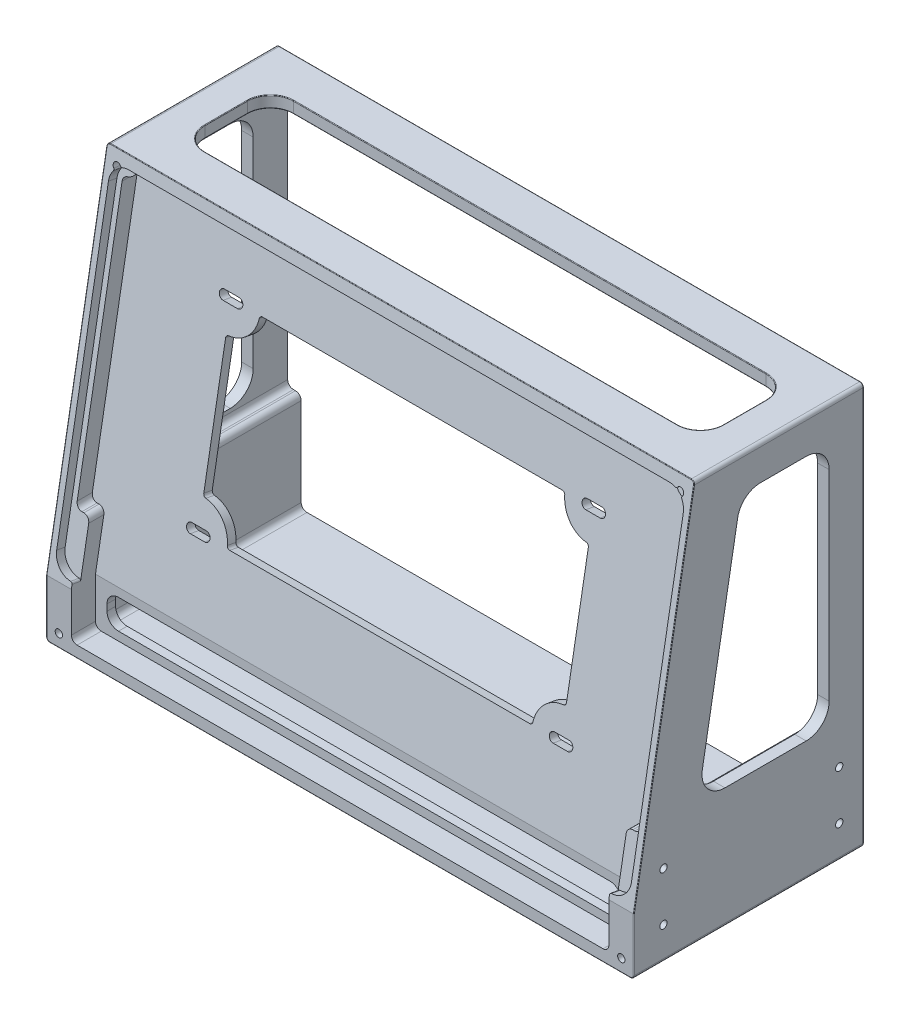
SolidWorks part; units mm, degrees
ref_plane "Спереди" through (0, 0, 0) normal (0, 0, 1) x (1, 0, 0)
ref_plane "Сверху" through (0, 0, 0) normal (0, 1, 0) x (1, 0, 0)
ref_plane "Справа" through (0, 0, 0) normal (1, 0, 0) x (0, 0, -1)
sketch "Эскиз2" plane through (0, 0, 0) normal (0, 0, 1) x (1, 0, 0)
  line L1 (102.25, -69.9) -> (-102.25, -69.9)
  line L2 (102.25, -69.9) -> (102.25, 69.9)
  line L3 (102.25, 69.9) -> (-102.25, 69.9)
  line L4 (-102.25, -69.9) -> (-102.25, 69.9)
  line L5 (102.25, -69.9) -> (-102.25, 69.9) construction
  line L6 (102.25, 69.9) -> (-102.25, -69.9) construction
  point P0 (0, 0)
  dimension "D1" = 204.5
  dimension "D2" = 139.8
extrude "Вытянуть-Тонкостенный1" add sketch "Эскиз2" along normal blind 80 thin
fillet "Скругление1" radius 1.2 8 edges at (98.25, -65.9, 40) (98.25, 65.9, 40) (-98.25, 65.9, 40) (-98.25, -65.9, 40) (-102.25, -69.9, 40) (102.25, -69.9, 40) (102.25, 69.9, 40) (-102.25, 69.9, 40)
sketch "Эскиз11" plane through (0, 0, 80) normal (0, 0, 1) x (1, 0, 0)
  line L0 (101.05, 69.9) -> (-101.05, 69.9) construction
  circle A0 centre (-97.8985, 65.5485) radius 4.3515
  arc A1 (-97.05, 65.9) -> (-98.25, 64.7) centre (-97.05, 64.7) ccw construction
  circle A2 centre (97.8985, 65.5485) radius 4.3515
  arc A3 (98.25, 64.7) -> (97.05, 65.9) centre (97.05, 64.7) ccw construction
  circle A4 centre (97.8985, -65.5485) radius 4.3515
  arc A5 (97.05, -65.9) -> (98.25, -64.7) centre (97.05, -64.7) ccw construction
  circle A6 centre (-97.8985, -65.5485) radius 4.3515
  arc A7 (-98.25, -64.7) -> (-97.05, -65.9) centre (-97.05, -64.7) ccw construction
extrude "Бобышка-Вытянуть6" add sketch "Эскиз11" against normal up to surface (80 mm away) up to face at (0, 0, 0)
sketch "Эскиз3" plane through (-102.25, 0, 0) normal (-1, 0, 0) x (0, 0, 1)
  line L0 (58.8408, 69.9) -> (80, -50.1)
  line L1 (0, 69.9) -> (80, 69.9) construction
  line L2 (80, 68.7) -> (80, -68.7) construction
  line L3 (80, -50.1) -> (80, 69.9)
  line L4 (80, 69.9) -> (58.8408, 69.9)
  dimension "D1" = 10
  dimension "D2" = 120
extrude "Вырез-Вытянуть1" cut sketch "Эскиз3" against normal through all
ref_plane "Плоскость1" through (0, 10.7462, 60.9447) normal (0, 0.1736, 0.9848) x (1, 0, 0)
sketch "Эскиз5" plane through (0, 10.7462, 60.9447) normal (0, 0.1736, 0.9848) x (1, 0, 0)
  line L0 (-52.3265, 30.618) -> (53.95, 30.618)
  line L1 (63.95, 30.618) -> (-62.3265, 30.618) construction
  line L3 (63.95, -35.032) -> (-62.3265, -35.032) construction
  line L4 (-62.3265, 30.618) -> (-62.3265, -35.032) construction
  line L5 (63.95, -35.032) -> (63.95, 30.618) construction
  line L6 (63.95, 20.618) -> (63.95, -25.032)
  line L7 (-62.3265, 20.618) -> (-62.3265, -25.032)
  line L16 (-52.3265, -35.032) -> (53.95, -35.032)
  line L17 (101.05, 58.6205) -> (-101.05, 58.6205) construction
  line L18 (-98.25, -63.2307) -> (-98.25, 49.7977) construction
  line L23 (98.25, -61.3795) -> (-98.25, -61.3795)
  line L24 (98.25, -61.3795) -> (98.25, 58.6205)
  line L25 (98.25, 58.6205) -> (-98.25, 58.6205)
  line L26 (-98.25, -61.3795) -> (-98.25, 58.6205)
  line L27 (98.25, -61.3795) -> (-98.25, 58.6205) construction
  line L28 (98.25, 58.6205) -> (-98.25, -61.3795) construction
  line L29 (98.25, 49.7977) -> (98.25, -63.2307) construction
  arc A0 (-62.3265, 20.618) -> (-52.3265, 30.618) centre (-62.3265, 30.618) ccw
  arc A1 (53.95, 30.618) -> (63.95, 20.618) centre (63.95, 30.618) ccw
  arc A2 (63.95, -25.032) -> (53.95, -35.032) centre (63.95, -35.032) ccw
  arc A3 (-52.3265, -35.032) -> (-62.3265, -25.032) centre (-62.3265, -35.032) ccw
  point P10 (0.8118, -1.3534)
  point P11 (0.8118, -1.3534)
  point P15 (0, -1.3795)
  dimension "D1" = 20
  dimension "D2" = 120
extrude "Бобышка-Вытянуть3" add sketch "Эскиз5" against normal blind 3
hole_wizard "Сверло под метчик  спиральное M31" positions "Трехмерный эскиз1" profile "Эскиз7" hole size "M3x0.5" standard "Ansi Metric"
sketch3d "Трехмерный эскиз1"
  line L0 (63.95, 40.3781, 52.6735) -> (63.95, 40.899, 55.6279) construction
  line L1 (-62.3265, 40.3781, 52.6735) -> (-62.3265, 40.899, 55.6279) construction
  line L2 (-62.3265, -24.2745, 64.0735) -> (-62.3265, -23.7536, 67.0279) construction
  line L3 (63.95, -24.2745, 64.0735) -> (63.95, -23.7536, 67.0279) construction
  point P0 (63.95, 40.3781, 52.6735)
  point P4 (-62.3265, 40.3781, 52.6735)
  point P8 (-62.3265, -24.2745, 64.0735)
  point P12 (63.95, -24.2745, 64.0735)
sketch "Эскиз7" plane through (63.95, 40.3781, 52.6735) normal (1, 0, 0) x (0, 0.9848, -0.1736)
  line L0 (0, 0) -> (0, 9.4464)
  line L1 (0, 9.4464) -> (1.575, 8.5)
  line L2 (1.575, 8.5) -> (1.575, 0)
  line L5 (1.575, 0) -> (0, 0)
  line L10 (0, 9.4464) -> (-1.575, 8.5) construction
  line L11 (0, -6.35) -> (0, 107.95) construction
  dimension "Диаметр отверстия" = 3.15
  dimension "Глубина отверстия" = 8.5
  dimension "Угол заточки сверла" = 118
hole_wizard "Сверло под метчик  спиральное M2.51" positions "Трехмерный эскиз2" profile "Эскиз12" hole size "M2.5x0.45" standard "Ansi Metric"
sketch3d "Трехмерный эскиз2"
  line L0 (97.8985, 65.5485, 14.6109) -> (97.8985, 65.5485, 44.282) construction
  line L1 (-97.8985, -65.5485, 0) -> (-97.8985, -65.5485, 80) construction
  line L2 (97.8985, -65.5485, 0) -> (97.8985, -65.5485, 80) construction
  line L3 (-97.8985, 65.5485, 14.6109) -> (-97.8985, 65.5485, 44.282) construction
  point P0 (97.8985, 65.5485, 0)
  point P8 (-97.8985, -65.5485, 0)
  point P31 (97.8985, -65.5485, 0)
  point P40 (-97.8985, 65.5485, 0)
sketch "Эскиз12" plane through (97.8985, 65.5485, 0) normal (1, 0, 0) x (0, 1, 0)
  line L0 (0, 0) -> (0, 20.7661)
  line L1 (0, 20.7661) -> (1.275, 20)
  line L2 (1.275, 20) -> (1.275, 0)
  line L5 (1.275, 0) -> (0, 0)
  line L10 (0, 20.7661) -> (-1.275, 20) construction
  line L11 (0, -6.35) -> (0, 107.95) construction
  dimension "Диаметр отверстия" = 2.55
  dimension "Глубина отверстия" = 20
  dimension "Угол заточки сверла" = 118
fillet "Скругление2" radius 1 8 edges at (53.95, -24.0141, 65.5507) (63.95, -14.166, 63.8142) (53.95, 40.6386, 54.1507) (63.95, 30.7905, 55.8872) (-52.3265, 40.6386, 54.1507) (-62.3265, 30.7905, 55.8872) (-52.3265, -24.0141, 65.5507) (-62.3265, -14.166, 63.8142)
hole_wizard "Сверло под метчик  спиральное M2.52" positions "Трехмерный эскиз3" profile "Эскиз13" hole size "M2.5x0.45" standard "Ansi Metric"
sketch3d "Трехмерный эскиз3"
  line L0 (-97.8985, -65.5485, 0) -> (-97.8985, -65.5485, 80) construction
  line L1 (97.8985, -65.5485, 0) -> (97.8985, -65.5485, 80) construction
  point P12 (-98.0213, 65.0213, 59.701)
  point P28 (98.0213, 65.0213, 59.701)
  point P36 (-97.8985, -65.5485, 80)
  point P40 (97.8985, -65.5485, 80)
sketch "Эскиз13" plane through (-98.0213, 65.0213, 59.701) normal (1, 0, 0) x (0, -0.9848, 0.1736)
  line L0 (0, 0) -> (0, 9.2661)
  line L1 (0, 9.2661) -> (1.275, 8.5)
  line L2 (1.275, 8.5) -> (1.275, 0)
  line L5 (1.275, 0) -> (0, 0)
  line L10 (0, 9.2661) -> (-1.275, 8.5) construction
  line L11 (0, -6.35) -> (0, 107.95) construction
  dimension "Диаметр отверстия" = 2.55
  dimension "Глубина отверстия" = 8.5
  dimension "Угол заточки сверла" = 118
sketch "Эскиз17" plane through (0, 0, 0) normal (0, 0, -1) x (-1, 0, 0)
  line L0 (-98.25, -31.2113) -> (-93.5471, -31.2113)
  line L1 (-98.25, -61.2113) -> (-98.25, 61.2113) construction
  line L2 (-93.5471, -65.5485) -> (-93.5471, -31.2113)
  line L4 (-98.25, -31.2113) -> (-98.25, -61.2113)
  line L5 (98.25, -61.2113) -> (98.25, -31.2113)
  line L6 (98.25, 61.2113) -> (98.25, -50.2218) construction
  line L7 (98.25, -31.2113) -> (93.5471, -31.2113)
  line L8 (93.5471, -31.2113) -> (93.5471, -65.5485)
  arc A0 (-93.5471, -65.5485) -> (-98.25, -61.2113) centre (-97.8985, -65.5485) ccw
  arc A1 (98.25, -61.2113) -> (93.5471, -65.5485) centre (97.8985, -65.5485) ccw
  dimension "D1" = 30
extrude "Бобышка-Вытянуть7" add sketch "Эскиз17" against normal up to surface (80 mm away) up to face at (-96.6235, -65.5485, 80)
fillet "Скругление3" radius 2 18 edges at (93.5471, -31.2113, 32.6483) (98.25, -31.2113, 32.6483) (-98.25, -31.2113, 32.6483) (-93.5471, -31.2113, 32.6483) (-93.5613, -65.9, 40) (93.5613, -65.9, 40) (-93.5613, 65.9, 24.0866) (-98.25, 61.2113, 24.5) (93.5613, 65.9, 24.0866) (98.25, 61.2113, 24.5) (-93.5471, -31.2113, 74.1715) (-98.25, -31.2113, 72.5062) (93.5471, -31.2113, 74.1715) (98.25, -31.2113, 72.5062) (98.25, 61.2113, 56.2096) (93.5613, 65.9, 55.3828) (-93.5613, 65.9, 55.3828) (-98.25, 61.2113, 56.2096)
hole_wizard "Сверло под метчик  спиральное M30" positions "Трехмерный эскиз5" profile "Эскиз16" hole size "M2.5x0.45" standard "Ansi Metric"
sketch3d "Трехмерный эскиз5"
  circle A0 centre (-104.05, -58.5, 8.4941) radius 1.7 construction
  circle A1 centre (-102.5, -41.5, 8.4941) radius 1.7 construction
  circle A2 centre (-104.05, -58.48, 69.6888) radius 1.7 construction
  circle A3 centre (-104.05, -41.5, 69.6541) radius 1.7 construction
  circle A4 centre (104.05, -58.5, 8.4941) radius 1.7 construction
  circle A5 centre (102.5, -41.5, 8.4941) radius 1.7 construction
  circle A6 centre (104.05, -58.48, 69.6888) radius 1.7 construction
  circle A7 centre (104.05, -41.5, 69.6541) radius 1.7 construction
  point P0 (-102.25, -58.5, 8.4941)
  point P2 (-102.25, -41.5, 8.4941)
  point P4 (-102.25, -41.5, 69.6541)
  point P6 (-102.25, -58.48, 69.6888)
  point P8 (102.25, -41.5, 69.6541)
  point P10 (102.25, -58.48, 69.6888)
  point P12 (102.25, -41.5, 8.4941)
  point P14 (102.25, -58.5, 8.4941)
  point P24 (-105.75, -58.5, 8.4941)
  point P29 (-100.8, -41.5, 8.4941)
  point P33 (-105.75, -58.48, 69.6888)
  point P37 (-105.75, -41.5, 69.6541)
  point P41 (105.75, -58.5, 8.4941)
  point P45 (100.8, -41.5, 8.4941)
  point P49 (105.75, -58.48, 69.6888)
  point P52 (105.75, -41.5, 69.6541)
sketch "Эскиз16" plane through (-102.25, -58.5, 8.4941) normal (0, 1, 0) x (0, 0, 1)
  line L0 (0, 0) -> (0, 7.7661)
  line L1 (0, 7.7661) -> (1.275, 7)
  line L2 (1.275, 7) -> (1.275, 0)
  line L5 (1.275, 0) -> (0, 0)
  line L10 (0, 7.7661) -> (-1.275, 7) construction
  line L11 (0, -6.35) -> (0, 107.95) construction
  dimension "Диаметр отверстия" = 2.55
  dimension "Глубина отверстия" = 7
  dimension "Угол заточки сверла" = 118
sketch "Эскиз18" plane through (-98.25, 0, 0) normal (-1, 0, 0) x (0, 0, 1)
  line L0 (80, -31.2113) -> (76.6694, -31.2113)
  line L1 (59.0524, 68.7) -> (80, -50.1) construction
  line L2 (80, -50.1) -> (76.6694, -31.2113) construction
  line L3 (76.6694, -31.2113) -> (80, -50.1)
  line L4 (80, -50.1) -> (80, -31.2113)
extrude "Вырез-Вытянуть2" cut sketch "Эскиз18" against normal through all
ref_plane "Плоскость2" through (0, 0, 71.6031) normal (0, 0, 1) x (1, 0, 0)
sketch "Эскиз19" plane through (0, 0, 71.6031) normal (0, 0, 1) x (1, 0, 0)
  line L0 (-91.5471, -65.9) -> (91.5471, -65.9) construction
  line L1 (-93.5471, -49.7008) -> (93.5471, -49.7008)
  line L2 (-93.5471, -49.7008) -> (-93.5471, -65.9)
  line L3 (-93.5471, -65.9) -> (93.5471, -65.9)
  line L4 (93.5471, -49.7008) -> (93.5471, -65.9)
extrude "Бобышка-Вытянуть8" add sketch "Эскиз19" against normal blind 3
sketch "Эскиз20" plane through (0, 0, 71.6031) normal (0, 0, 1) x (1, 0, 0)
  line L3 (0, 0) -> (0, -65.9) construction
  line L4 (-91.5471, -65.9) -> (91.5471, -65.9) construction
  line L12 (-93.5471, -49.7008) -> (93.5471, -49.7008) construction
  line L13 (89.5471, -62.9) -> (-89.5471, -62.9)
  line L14 (89.5471, -62.9) -> (89.5471, -52.7008)
  line L15 (89.5471, -52.7008) -> (-89.5471, -52.7008)
  line L16 (-89.5471, -62.9) -> (-89.5471, -52.7008)
  line L17 (89.5471, -62.9) -> (-89.5471, -52.7008) construction
  line L18 (89.5471, -52.7008) -> (-89.5471, -62.9) construction
  line L19 (-91.5471, -65.9) -> (91.5471, -65.9) construction
  line L20 (-93.5471, -50.1) -> (-93.5471, -63.9) construction
  point P0 (0, -57.8004)
  point P14 (-89.5471, -57.8004)
  dimension "D1" = 3
  dimension "D2" = 3
  dimension "D3" = 4
extrude "Вырез-Вытянуть3" cut sketch "Эскиз20" against normal blind 4
hole_wizard "Цековка для винта с внутренним шестигранником M31" positions "Трехмерный эскиз6" profile "Эскиз21" counterbore size "M3" standard "Ansi Metric"
sketch3d "Трехмерный эскиз6"
  circle A0 centre (34.7971, -65.9, 34.3016) radius 1.5 construction
  circle A1 centre (73.8971, -65.9, 34.3016) radius 1.5 construction
  point P16 (34.7971, -69.9, 34.3016)
  point P28 (34.7971, -67.4, 34.3016)
  point P31 (73.8971, -69.9, 34.3016)
  point P38 (73.8971, -67.4, 34.3016)
sketch "Эскиз21" plane through (34.7971, -69.9, 34.3016) normal (1, 0, 0) x (0, 0, -1)
  line L0 (0, 0) -> (0, 9.5215)
  line L1 (0, 9.5215) -> (1.7, 8.5)
  line L2 (1.7, 8.5) -> (1.7, 3)
  line L3 (1.7, 3) -> (3.25, 3)
  line L4 (3.25, 3) -> (3.25, 0)
  line L5 (3.25, 0) -> (0, 0)
  line L10 (0, 9.5215) -> (-1.7, 8.5) construction
  line L11 (0, -6.35) -> (0, 107.95) construction
  dimension "Диаметр отверстия" = 3.4
  dimension "Глубина отверстия" = 8.5
  dimension "Диаметр цековки" = 6.5
  dimension "Глубина цековки" = 3
  dimension "Угол заточки сверла" = 118
sketch "Эскиз22" plane through (0, 69.9, 0) normal (0, 1, 0) x (1, 0, 0)
  line L0 (101.05, 0) -> (-101.05, 0) construction
  line L1 (-90.25, -14) -> (90.25, -14)
  line L2 (-90.25, -14) -> (-90.25, -44.8408)
  line L3 (-90.25, -44.8408) -> (90.25, -44.8408)
  line L4 (90.25, -14) -> (90.25, -44.8408)
  line L5 (101.05, -58.8408) -> (-101.05, -58.8408) construction
  line L6 (-102.25, -59.0524) -> (-102.25, 0) construction
  line L7 (102.25, 0) -> (102.25, -59.0524) construction
  dimension "D1" = 14
  dimension "D2" = 14
  dimension "D3" = 12
  dimension "D4" = 12
extrude "Вырез-Вытянуть4" cut sketch "Эскиз22" against normal up to surface (4 mm away) up to face at (0, 65.9, 24.0866)
sketch "Эскиз23" plane through (102.25, 0, 0) normal (1, 0, 0) x (0, 0, -1)
  line L0 (-42.679, 57.9) -> (-12, 57.9)
  line L1 (-12, 57.9) -> (-12, -27.9)
  line L2 (-12, -27.9) -> (-57.8079, -27.9)
  line L3 (-57.8079, -27.9) -> (-42.679, 57.9)
  line L4 (-59.0524, 68.7) -> (-80, -50.1) construction
  line L5 (-58.8408, 69.9) -> (0, 69.9) construction
  line L6 (0, -69.9) -> (-80, -69.9) construction
  line L7 (0, -68.7) -> (0, 68.7) construction
  dimension "D1" = 12
  dimension "D2" = 42
  dimension "D3" = 12
  dimension "D4" = 18
extrude "Вырез-Вытянуть5" cut sketch "Эскиз23" against normal through all
fillet "Скругление26" radius 8 12 edges at (90.25, 67.9, 14) (90.25, 67.9, 44.8408) (-90.25, 67.9, 44.8408) (-90.25, 67.9, 14) (-100.25, -27.9, 12) (-100.25, -27.9, 57.8079) (-100.25, 57.9, 12) (-100.25, 57.9, 42.679) (100.25, 57.9, 12) (100.25, 57.9, 42.679) (100.25, -27.9, 12) (100.25, -27.9, 57.8079)
fillet "Скругление27" radius 0.2 34 edges at (101.8985, 69.5485, 58.9027) (101.8985, 69.5485, 0) (102.25, 0, 0) (101.8985, -69.5485, 80) (101.8985, -69.5485, 0) (0, -69.9, 0) (0, -69.9, 80) (-101.8985, -69.5485, 80) (-101.8985, -69.5485, 0) (-102.25, 0, 0) (-101.8985, 69.5485, 58.9027) (-101.8985, 69.5485, 0) (102.25, -59.4, 80) (102.25, 9.3, 69.5262) (-102.25, 9.3, 69.5262) (0, 69.9, 58.8408) (0, 69.9, 0) (-102.25, -59.4, 80) (-87.9069, 65.9, 42.4976) (-90.25, 65.9, 29.4204) (-87.9069, 65.9, 16.3431) (0, 65.9, 14) (87.9069, 65.9, 16.3431) (90.25, 65.9, 29.4204) (87.9069, 65.9, 42.4976) (-87.9069, 69.9, 42.4976) (-90.25, 69.9, 29.4204) (-87.9069, 69.9, 16.3431) (0, 69.9, 14) (87.9069, 69.9, 16.3431) (90.25, 69.9, 29.4204) (87.9069, 69.9, 42.4976) (0, 65.9, 44.8408) (0, 69.9, 44.8408)
sketch "Эскиз27" plane through (0, 12.1701, 69.0201) normal (0, 0.1736, 0.9848) x (1, 0, 0)
  line L0 (-98.25, -42.0198) -> (-98.25, 47.9734) construction
  line L1 (-94.05, 54.5588) -> (94.05, 54.5588)
  line L2 (-100.05, 48.5588) -> (-100.05, -55.2307)
  line L3 (-94.05, -61.2307) -> (94.05, -61.2307)
  line L4 (100.05, 48.5588) -> (100.05, -55.2307)
  line L5 (-102.05, 57.4372) -> (-102.05, -63.2307) construction
  line L6 (102.05, -63.2307) -> (102.05, 57.4372) construction
  line L8 (-93.5471, -63.2307) -> (-102.05, -63.2307) construction
  line L9 (-91.7647, 54.5588) -> (91.7647, 54.5588) construction
  arc A0 (100.05, 48.5588) -> (94.05, 54.5588) centre (94.05, 48.5588) ccw
  arc A1 (-100.05, 48.5588) -> (-94.05, 54.5588) centre (-94.05, 48.5588) cw
  arc A2 (94.05, -61.2307) -> (100.05, -55.2307) centre (94.05, -55.2307) ccw
  arc A3 (-94.05, -61.2307) -> (-100.05, -55.2307) centre (-94.05, -55.2307) cw
  point P14 (-98.25, 54.5588)
  dimension "D2" = 6
  dimension "D3" = 6
  dimension "D1" = 2
  dimension "D4" = 2
  dimension "D5" = 2
extrude "Вырез-Вытянуть8" cut sketch "Эскиз27" against normal blind 3
fillet "Скругление32" radius 4 4 edges at (89.5471, -52.7008, 70.1031) (89.5471, -62.9, 70.1031) (-89.5471, -52.7008, 70.1031) (-89.5471, -62.9, 70.1031)
sketch "Эскиз28" plane through (0, 10.7462, 60.9447) normal (0, 0.1736, 0.9848) x (1, 0, 0)
  line L0 (-59.8265, 30.618) -> (-64.8265, 30.618) construction
  line L1 (-59.8265, 29.043) -> (-64.8265, 29.043)
  line L2 (-59.8265, 32.193) -> (-64.8265, 32.193)
  line L3 (66.45, 30.618) -> (61.45, 30.618) construction
  line L4 (66.45, 29.043) -> (61.45, 29.043)
  line L5 (66.45, 32.193) -> (61.45, 32.193)
  line L6 (66.45, -35.032) -> (61.45, -35.032) construction
  line L7 (66.45, -36.607) -> (61.45, -36.607)
  line L8 (66.45, -33.457) -> (61.45, -33.457)
  line L9 (-59.8265, -35.032) -> (-64.8265, -35.032) construction
  line L10 (-59.8265, -36.607) -> (-64.8265, -36.607)
  line L11 (-59.8265, -33.457) -> (-64.8265, -33.457)
  arc A0 (-59.8265, 29.043) -> (-59.8265, 32.193) centre (-59.8265, 30.618) ccw
  arc A1 (-64.8265, 32.193) -> (-64.8265, 29.043) centre (-64.8265, 30.618) ccw
  arc A2 (66.45, 29.043) -> (66.45, 32.193) centre (66.45, 30.618) ccw
  arc A3 (61.45, 32.193) -> (61.45, 29.043) centre (61.45, 30.618) ccw
  arc A4 (66.45, -36.607) -> (66.45, -33.457) centre (66.45, -35.032) ccw
  arc A5 (61.45, -33.457) -> (61.45, -36.607) centre (61.45, -35.032) ccw
  arc A6 (-59.8265, -36.607) -> (-59.8265, -33.457) centre (-59.8265, -35.032) ccw
  arc A7 (-64.8265, -33.457) -> (-64.8265, -36.607) centre (-64.8265, -35.032) ccw
  circle A8 centre (-62.3265, 30.618) radius 1.575 construction
  point P2 (-62.3265, 30.618)
  point P9 (63.95, 30.618)
  point P17 (63.95, -35.032)
  point P25 (-62.3265, -35.032)
  dimension "D1" = 5
extrude "Вырез-Вытянуть9" cut sketch "Эскиз28" against normal up to surface (3 mm away)
fillet "Скругление33" radius 0.6 6 edges at (93.5471, -48.3909, 78.1755) (-93.5471, -48.3909, 78.1755) (98.5632, 63.6243, 58.4242) (96.7692, 64.9979, 58.182) (-96.7692, 64.9979, 58.182) (-98.5632, 63.6243, 58.4242)
